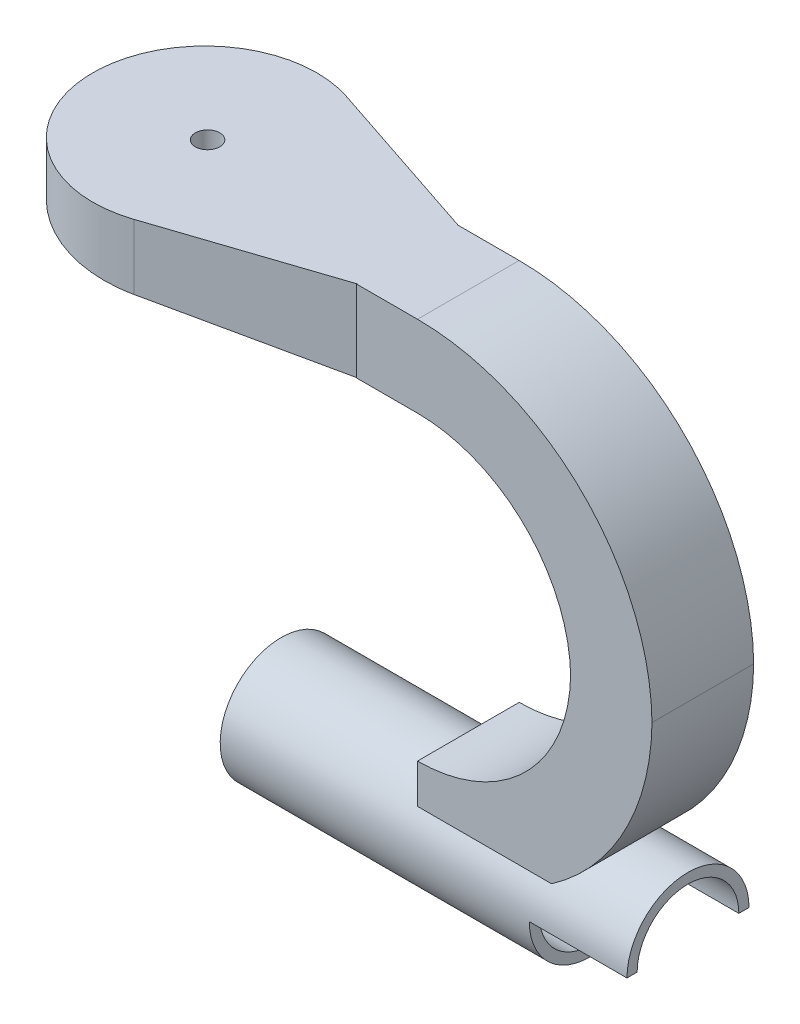
SolidWorks part; units mm, degrees
material "ABS"
ref_plane "Front Plane" through (0, 0, 0) normal (0, 0, 1) x (1, 0, 0)
ref_plane "Top Plane" through (0, 0, 0) normal (0, 1, 0) x (1, 0, 0)
ref_plane "Right Plane" through (0, 0, 0) normal (1, 0, 0) x (0, 0, -1)
sketch "Sketch1" plane through (0, 0, 0) normal (0, 0, 1) x (1, 0, 0)
  line L0 (-64.2401, 0) -> (67.2222, 0) construction
  line L1 (-32.0579, -37.0332) -> (-32.0579, -57.0332)
  line L2 (-32.0579, 37.0332) -> (-32.0579, 57.0332)
  line L4 (-32.0579, 57.0332) -> (-47.0579, 57.0332)
  line L5 (-32.0579, 57.0332) -> (-32.0579, 37.0332)
  line L6 (-32.0579, 37.0332) -> (-47.0579, 37.0332)
  line L7 (-47.0579, 57.0332) -> (-47.0579, 37.0332)
  arc A0 (-32.0579, -57.0332) -> (25.5933, 0) centre (-32.0579, 0.6213) ccw
  arc A1 (-32.0579, -37.0332) -> (5.5915, 0) centre (-32.0579, 0.6213) ccw
  arc A2 (-32.0579, 37.0332) -> (5.5915, 0) centre (-32.0579, -0.6213) cw
  arc A3 (-32.0579, 57.0332) -> (25.5933, 0) centre (-32.0579, -0.6213) cw
  dimension "D1" = 20
  dimension "D2" = 15
extrude "Boss-Extrude2" add sketch "Sketch1" along normal blind 25 contours L0 A1 L1 A0 | A2 L0 A3 L2 | L4 L7 L6 L2 region at (-1.416, 30.4169, 0) region at (-1.416, -30.4169, 0) region at (-39.5579, 47.0332, 0)
sketch "Sketch2" plane through (-32.0579, 0, 0) normal (-1, 0, 0) x (0, 0, 1)
  line L0 (25, 57.0332) -> (0, 57.0332) construction
  line L2 (25, -37.0332) -> (25, -57.0332) construction
  circle A0 centre (12.5, -54.9668) radius 15
  dimension "D1" = 30
  dimension "D2" = 112
  dimension "D3" = 12.5
ref_plane "Plane1" through (0, 57.0332, 0) normal (0, 1, 0) x (1, 0, 0)
sketch "Sketch3" plane through (0, 57.0332, 0) normal (0, 1, 0) x (1, 0, 0)
  line L0 (-47.0579, -12.5) -> (-121.2512, -12.5) construction
  line L1 (-47.0579, -25) -> (-47.0579, 0) construction
  line L2 (-47.0579, 0) -> (-88.1889, 13.6904)
  line L3 (-88.1889, -38.5916) -> (-47.0579, -24.9012)
  line L4 (-47.0579, 0) -> (-47.0579, -24.9012)
  arc A0 (-88.1889, 13.6904) -> (-88.1889, -38.5916) centre (-96.8898, -12.4506) ccw
extrude "Boss-Extrude4" add sketch "Sketch3" against normal blind 20 contours L0 | L0 | L4 L3 A0 L2
extrude "Boss-Extrude5" add sketch "Sketch2" along normal blind 46 and the other way blind 54
sketch "Sketch5" plane through (21.9421, 0, 0) normal (1, 0, 0) x (0, 0, -1)
  line L0 (0, -54.9668) -> (2.5, -54.9668)
  line L1 (-25, -54.9668) -> (-27.5, -54.9668)
  circle A0 centre (-12.5, -54.9668) radius 12.5
  circle A1 centre (-12.5, -54.9668) radius 15 construction
  circle A2 centre (-12.5, -54.9668) radius 15
  circle M2 centre (-12.5, -54.9668) radius 15
extrude "Cut-Extrude1" cut sketch "Sketch5" against normal blind 95 contours A0 A2 region at (21.9421, -54.9668, 12.5)
sketch "Sketch6" plane through (0, 57.0332, 0) normal (0, 1, 0) x (1, 0, 0)
  line L0 (-32.0579, -25) -> (-32.0579, 0) construction
  line L1 (-32.0579, -12.5) -> (-96.0522, -12.6061) construction
  circle A0 centre (-96.0522, -12.6061) radius 3
  dimension "D1" = 6
extrude "Cut-Extrude2" cut sketch "Sketch6" against normal blind 24
sketch "Sketch7" plane through (0, 0, 0) normal (0, 0, 1) x (1, 0, 0)
  line L0 (-124.4409, 44.5718) -> (-47.0579, 37.0332)
  line L1 (-124.4409, 57.0332) -> (-124.4409, 37.0332) construction
  line L2 (-88.1889, 37.0332) -> (-47.0579, 37.0332) construction
  line L3 (-47.0579, 37.0332) -> (-124.4409, 37.0332)
  line L4 (-124.4409, 37.0332) -> (-124.4409, 44.5718)
extrude "Cut-Extrude3" cut sketch "Sketch7" against normal through all both and the other way through all
extrude "Cut-Extrude5" cut sketch "Sketch5<3>" against normal blind 24 contours A0 L1 L0 M2 region at (21.9421, -55.3022, -1.25)
sketch "Sketch5<3>" plane through (21.9421, 0, 0) normal (1, 0, 0) x (0, 0, -1) same geometry as "Sketch5"
sketch "Sketch11" plane through (-78.0579, 0, 0) normal (-1, 0, 0) x (0, 0, 1)
  circle A0 centre (14.6722, -59.1685) radius 2.435
  circle A1 centre (12.5, -54.9668) radius 15
  circle A2 centre (12.5, -54.9668) radius 15
  circle A3 centre (12.5, -54.9668) radius 15 construction
  dimension "D3" = 4.87
  dimension "D2" = 4.73
  dimension "D4" = 2.1722
  dimension "D1" = 0
sketch "Sketch12" plane through (-78.0579, 0, 0) normal (-1, 0, 0) x (0, 0, 1)
  circle A0 centre (12.5, -54.9668) radius 15
  circle A1 centre (12.5, -54.9668) radius 15 construction
extrude "Cut-Extrude6" cut sketch "Sketch11" against normal through all contours A0 region at (-78.0579, -59.1685, 14.6722)
sketch "Sketch13" plane through (0, 57.0332, 0) normal (0, 1, 0) x (1, 0, 0)
  line L0 (-96.0522, -12.6061) -> (-96.0522, 3.1296) construction
  line L1 (-96.0522, -7.7948) -> (-100.2189, -10.2005)
  line L2 (-100.2189, -10.2005) -> (-100.2189, -15.0117)
  line L3 (-100.2189, -15.0117) -> (-96.0522, -17.4174)
  line L4 (-96.0522, -17.4174) -> (-91.8855, -15.0117)
  line L5 (-91.8855, -15.0117) -> (-91.8855, -10.2005)
  line L6 (-91.8855, -10.2005) -> (-96.0522, -7.7948)
  circle A0 centre (-96.0522, -12.6061) radius 4.1667 construction
  circle A1 centre (-96.0522, -12.6061) radius 3 construction
  dimension "D1" = 8.3333
extrude "Cut-Extrude7" cut sketch "Sketch13" against normal blind 10 from offset 12 offset against normal yes
